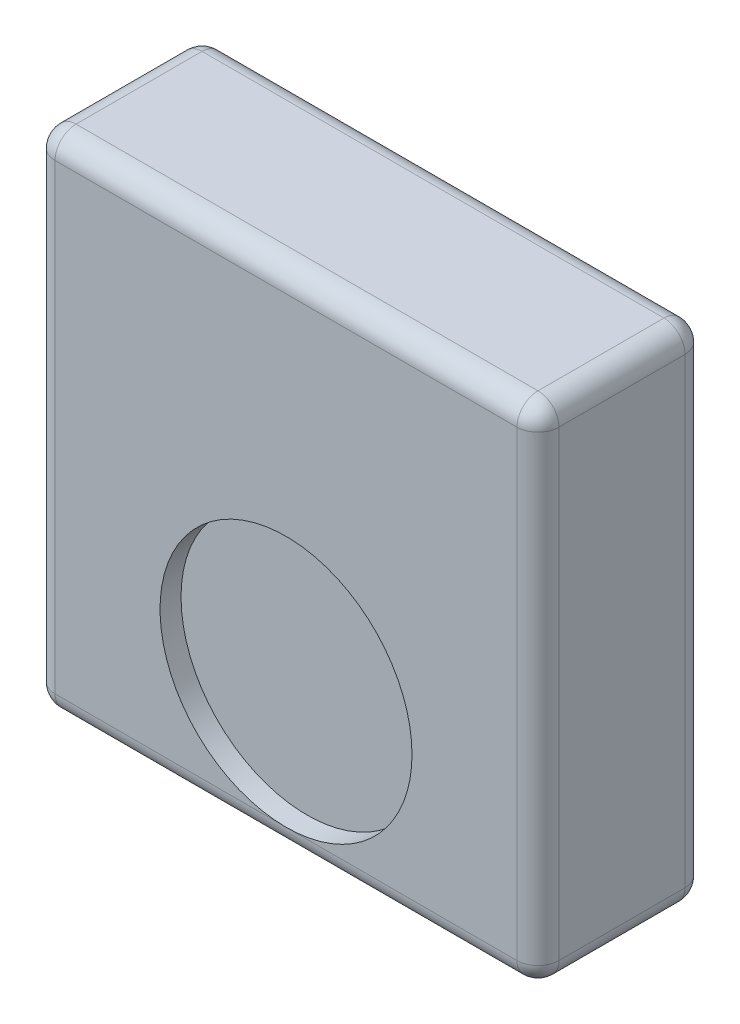
SolidWorks part; units mm, degrees
ref_plane "Front Plane" through (0, 0, 0) normal (0, 0, 1) x (1, 0, 0)
ref_plane "Top Plane" through (0, 0, 0) normal (0, 1, 0) x (1, 0, 0)
ref_plane "Right Plane" through (0, 0, 0) normal (1, 0, 0) x (0, 0, -1)
sketch "Sketch1" plane through (0, 0, 0) normal (0, 0, 1) x (1, 0, 0)
  line L1 (-76.2, -76.2) -> (76.2, -76.2)
  line L2 (-76.2, -76.2) -> (-76.2, 76.2)
  line L3 (-76.2, 76.2) -> (76.2, 76.2)
  line L4 (76.2, -76.2) -> (76.2, 76.2)
  line L5 (0, 76.2) -> (0, -76.2) construction
  line L6 (-76.2, 0) -> (76.2, 0) construction
  point P0 (0, 0)
  dimension "D1" = 152.4
extrude "Boss-Extrude1" add sketch "Sketch1" along normal mid plane 50.8
sketch "Sketch2" plane through (0, 0, 25.4) normal (0, 0, 1) x (1, 0, 0)
  line L0 (-76.2, -76.2) -> (76.2, -76.2) construction
  circle A0 centre (0, -31.75) radius 38.1
  dimension "D1" = 76.2
  dimension "D2" = 6.35
extrude "Cut-Extrude1" cut sketch "Sketch2" against normal blind 6.35
fillet "Fillet1" radius 6.35 12 edges at (76.2, 0, 25.4) (76.2, 76.2, 0) (0, 76.2, 25.4) (0, 76.2, -25.4) (76.2, 0, -25.4) (0, -76.2, 25.4) (76.2, -76.2, 0) (0, -76.2, -25.4) (-76.2, 76.2, 0) (-76.2, 0, 25.4) (-76.2, -76.2, 0) (-76.2, 0, -25.4)
